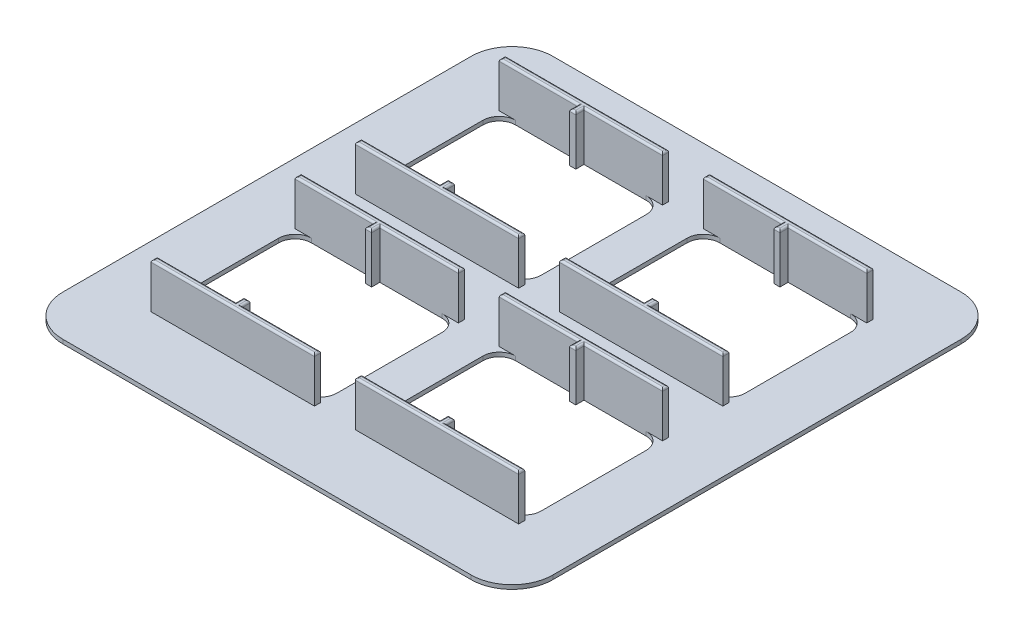
SolidWorks part; units mm, degrees
ref_plane "Front Plane" through (0, 0, 0) normal (0, 0, 1) x (1, 0, 0)
ref_plane "Top Plane" through (0, 0, 0) normal (0, 1, 0) x (1, 0, 0)
ref_plane "Right Plane" through (0, 0, 0) normal (1, 0, 0) x (0, 0, -1)
sketch "Sketch6" plane through (0, 0, 0) normal (0, 1, 0) x (1, 0, 0)
  line L1 (60, -60) -> (-60, -60)
  line L2 (60, -60) -> (60, 60)
  line L3 (60, 60) -> (-60, 60)
  line L4 (-60, -60) -> (-60, 60)
  line L5 (60, -60) -> (-60, 60) construction
  line L6 (60, 60) -> (-60, -60) construction
  point P0 (0, 0)
  dimension "D1" = 120
extrude "Boss-Extrude5" add sketch "Sketch6" along normal blind 1
sketch "Sketch7" plane through (0, 1, 0) normal (0, 1, 0) x (1, 0, 0)
  line L1 (25, -25) -> (-25, -25)
  line L2 (25, -25) -> (25, 25)
  line L3 (25, 25) -> (-25, 25)
  line L4 (-25, -25) -> (-25, 25)
  line L5 (25, -25) -> (-25, 25) construction
  line L6 (25, 25) -> (-25, -25) construction
  point P0 (0, 0)
  dimension "D1" = 50
sketch "Sketch3" plane through (0, 0, 0) normal (0, 1, 0) x (1, 0, 0)
  line L0 (-1000, 0) -> (49000, 0) construction
  line L1 (-5, 41.875) -> (-45, 41.875)
  line L2 (-5, 41.875) -> (-5, 43.375)
  line L3 (-5, 43.375) -> (-45, 43.375)
  line L4 (-45, 41.875) -> (-45, 43.375)
  line L5 (-5, 41.875) -> (-45, 43.375) construction
  line L6 (-5, 43.375) -> (-45, 41.875) construction
  line L7 (-5, 6.625) -> (-45, 6.625)
  line L8 (-5, 6.625) -> (-5, 8.125)
  line L9 (-5, 8.125) -> (-45, 8.125)
  line L10 (-45, 6.625) -> (-45, 8.125)
  line L11 (-5, 6.625) -> (-45, 8.125) construction
  line L12 (-5, 8.125) -> (-45, 6.625) construction
  line L13 (-25, 42.625) -> (-25, 7.375) construction
  point P0 (-25, 42.625)
  point P5 (-25, 7.375)
  point P10 (-25, 25)
  point P12 (0, 0)
  dimension "D1" = 33.75
  dimension "D2" = 1.5
  dimension "D3" = 40
extrude "Boss-Extrude2" add sketch "Sketch3" along normal blind 12
sketch "Sketch4" plane through (0, 0, 0) normal (0, 1, 0) x (1, 0, 0)
  line L1 (-24.25, 39.875) -> (-25.75, 39.875)
  line L2 (-24.25, 39.875) -> (-24.25, 41.875)
  line L3 (-24.25, 41.875) -> (-25.75, 41.875)
  line L4 (-25.75, 39.875) -> (-25.75, 41.875)
  line L5 (-24.25, 39.875) -> (-25.75, 41.875) construction
  line L6 (-24.25, 41.875) -> (-25.75, 39.875) construction
  line L7 (-24.25, 8.125) -> (-25.75, 8.125)
  line L8 (-24.25, 8.125) -> (-24.25, 10.125)
  line L9 (-24.25, 10.125) -> (-25.75, 10.125)
  line L10 (-25.75, 8.125) -> (-25.75, 10.125)
  line L11 (-24.25, 8.125) -> (-25.75, 10.125) construction
  line L12 (-24.25, 10.125) -> (-25.75, 8.125) construction
  line L13 (-45, 41.875) -> (-5, 41.875) construction
  line L14 (-5, 8.125) -> (-45, 8.125) construction
  line L15 (-5, 41.875) -> (-45, 41.875) construction
  point P0 (-25, 40.875)
  point P5 (-25, 9.125)
  point P10 (0, 0)
  point P20 (-25, 41.875)
  dimension "D1" = 1.5
  dimension "D2" = 2
extrude "Boss-Extrude3" add sketch "Sketch4" along normal up to surface (12 mm away) up to face at (-25, 12, -7.375)
sketch "Sketch8" plane through (0, 1, 0) normal (0, 1, 0) x (1, 0, 0)
  line L2 (-5, 8.125) -> (-5, 41.875)
  line L4 (-45, 8.125) -> (-45, 41.875)
  line L5 (-5, 8.125) -> (-45, 41.875) construction
  line L6 (-5, 41.875) -> (-45, 8.125) construction
  line L7 (-45, 41.875) -> (-25.75, 41.875) construction
  line L8 (-45, 8.125) -> (-25.75, 8.125) construction
  line L9 (-25.75, 10.125) -> (-25.75, 8.125) construction
  line L10 (-24.25, 10.125) -> (-25.75, 10.125) construction
  line L11 (-24.25, 10.125) -> (-24.25, 8.125) construction
  line L12 (-24.25, 8.125) -> (-5, 8.125) construction
  line L13 (-45, 8.125) -> (-25.75, 8.125)
  line L14 (-25.75, 10.125) -> (-25.75, 8.125)
  line L15 (-24.25, 10.125) -> (-25.75, 10.125)
  line L16 (-24.25, 10.125) -> (-24.25, 8.125)
  line L17 (-24.25, 8.125) -> (-5, 8.125)
  line L18 (-5, 41.875) -> (-24.25, 41.875) construction
  line L19 (-24.25, 41.875) -> (-24.25, 39.875) construction
  line L20 (-24.25, 39.875) -> (-25.75, 39.875) construction
  line L21 (-25.75, 39.875) -> (-25.75, 41.875) construction
  line L22 (-5, 41.875) -> (-24.25, 41.875)
  line L23 (-24.25, 41.875) -> (-24.25, 39.875)
  line L24 (-24.25, 39.875) -> (-25.75, 39.875)
  line L25 (-25.75, 39.875) -> (-25.75, 41.875)
  line L26 (-45, 41.875) -> (-25.75, 41.875)
  point P0 (-25, 25)
  point P10 (0, 0)
  point P11 (0, 0)
extrude "Cut-Extrude1" cut sketch "Sketch8" against normal through all
fillet "Fillet2" radius 0.5 16 edges at (-35.375, 12, -8.125) (-25.75, 12, -9.125) (-25, 12, -10.125) (-24.25, 12, -9.125) (-14.625, 12, -8.125) (-5, 12, -7.375) (-25, 12, -6.625) (-45, 12, -7.375) (-25, 12, -43.375) (-5, 12, -42.625) (-14.625, 12, -41.875) (-24.25, 12, -40.875) (-25, 12, -39.875) (-25.75, 12, -40.875) (-35.375, 12, -41.875) (-45, 12, -42.625)
fillet "Fillet4" radius 4 4 edges at (-5, 0.5, -8.125) (-45, 0.5, -8.125) (-5, 0.5, -41.875) (-45, 0.5, -41.875)
pattern_linear "LPattern5" count 2 spacing 50 along (1, 0, 0) count 2 spacing 50 along (0, 0, 1) of "Boss-Extrude2", "Boss-Extrude3", "Fillet2", "Cut-Extrude1", "Fillet4"
fillet "Fillet3" radius 10 4 edges at (-60, 0.5, -60) (60, 0.5, -60) (60, 0.5, 60) (-60, 0.5, 60)
